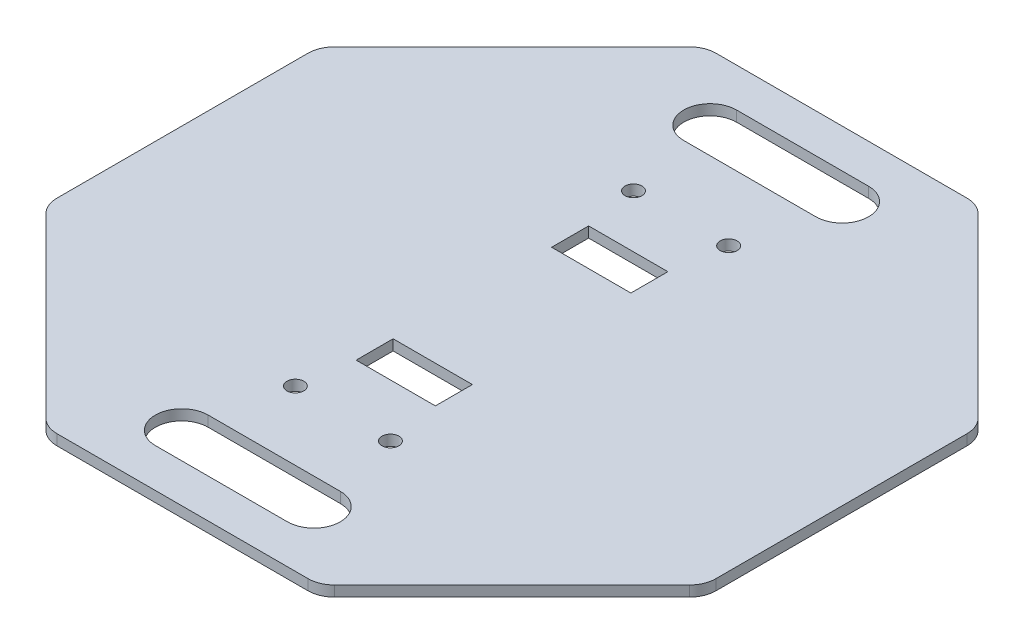
SolidWorks part; units mm, degrees
ref_plane "Front Plane" through (0, 0, 0) normal (0, 0, 1) x (1, 0, 0)
ref_plane "Top Plane" through (0, 0, 0) normal (0, 1, 0) x (1, 0, 0)
ref_plane "Right Plane" through (0, 0, 0) normal (1, 0, 0) x (0, 0, -1)
sketch "Sketch1" plane through (0, 0, 0) normal (0, 1, 0) x (1, 0, 0)
  line L0 (0, 67.5) -> (0, -67.5) construction
  line L1 (-67.5, 0) -> (67.5, 0) construction
  line L2 (62.3619, 25.8311) -> (62.3619, -25.8311)
  line L3 (-25.8311, 62.3619) -> (25.8311, 62.3619)
  line L4 (0, 0) -> (62.3619, 25.8311) construction
  line L5 (-25.8311, 62.3619) -> (0, 0) construction
  line L6 (-25.8311, -62.3619) -> (25.8311, -62.3619)
  line L7 (-62.3619, 25.8311) -> (-62.3619, -25.8311)
  line L8 (12.5, -50) -> (-12.5, -50) construction
  line L9 (12.5, -55) -> (-12.5, -55)
  line L10 (12.5, -45) -> (-12.5, -45)
  line L11 (12.5, 50) -> (-12.5, 50) construction
  line L12 (12.5, 55) -> (-12.5, 55)
  line L13 (12.5, 45) -> (-12.5, 45)
  line L14 (14.3249, -32) -> (-21.367, -32) construction
  line L15 (-7.5, -22) -> (7.5, -22)
  line L16 (-7.5, -22) -> (-7.5, -15)
  line L17 (-7.5, -15) -> (7.5, -15)
  line L18 (7.5, -22) -> (7.5, -15)
  line L19 (-7.5, -22) -> (7.5, -15) construction
  line L20 (-7.5, -15) -> (7.5, -22) construction
  line L21 (-7.5, 22) -> (-7.5, 15)
  line L22 (-7.5, 22) -> (7.5, 22)
  line L23 (7.5, 22) -> (7.5, 15)
  line L24 (-7.5, 15) -> (7.5, 15)
  line L25 (25.8311, -62.3619) -> (62.3619, -25.8311)
  line L26 (62.3619, 25.8311) -> (25.8311, 62.3619)
  line L27 (-25.8311, 62.3619) -> (-62.3619, 25.8311)
  line L28 (-62.3619, -25.8311) -> (-25.8311, -62.3619)
  circle A0 centre (0, 0) radius 67.5
  arc A1 (12.5, -55) -> (12.5, -45) centre (12.5, -50) ccw
  arc A2 (-12.5, -45) -> (-12.5, -55) centre (-12.5, -50) ccw
  arc A3 (12.5, 55) -> (12.5, 45) centre (12.5, 50) cw
  arc A4 (-12.5, 45) -> (-12.5, 55) centre (-12.5, 50) cw
  circle A5 centre (9, -32) radius 1.6
  circle A6 centre (-9, -32) radius 1.6
  circle A7 centre (-9, 32) radius 1.6
  circle A8 centre (9, 32) radius 1.6
  point P17 (0, -50)
  point P24 (0, 50)
  point P29 (0, -18.5)
  dimension "D1" = 135
  dimension "D10" = 3.2
  dimension "D11" = 9
  dimension "D12" = 32
  dimension "D2" = 22.5
  dimension "D3" = 22.5
  dimension "D4" = 10
  dimension "D5" = 25
  dimension "D6" = 50
  dimension "D7" = 7
  dimension "D8" = 23
  dimension "D9" = 15
extrude "Boss-Extrude1" add sketch "Sketch1" along normal blind 2 contours L6 A0 L2 L3 L7 region at (0, 0, 0)
fillet "Fillet1" radius 5 8 edges at (-25.8311, 1, 62.3619) (-62.3619, 1, 25.8311) (-62.3619, 1, -25.8311) (-25.8311, 1, -62.3619) (25.8311, 1, -62.3619) (62.3619, 1, -25.8311) (62.3619, 1, 25.8311) (25.8311, 1, 62.3619)
